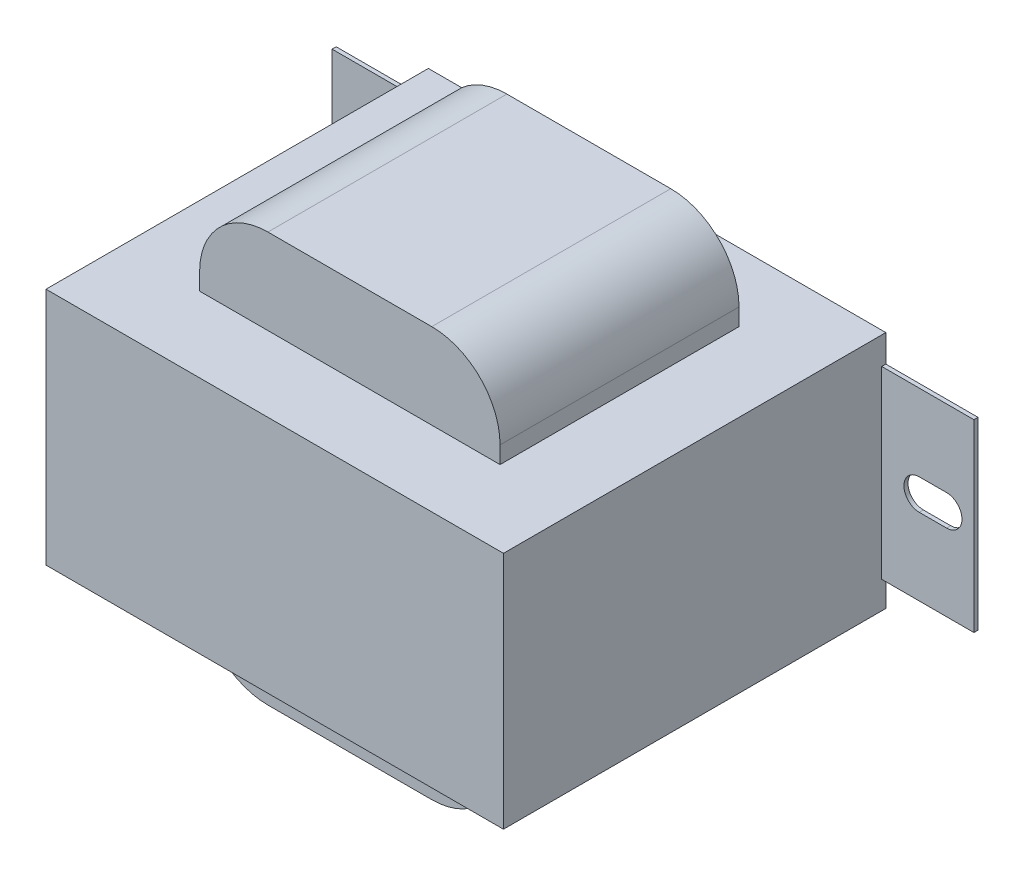
SolidWorks part; units mm, degrees
ref_plane "前视基准面" through (0, 0, 0) normal (0, 0, 1) x (1, 0, 0)
ref_plane "上视基准面" through (0, 0, 0) normal (0, 1, 0) x (1, 0, 0)
ref_plane "右视基准面" through (0, 0, 0) normal (1, 0, 0) x (0, 0, -1)
sketch "草图1" plane through (0, 0, 0) normal (0, 0, 1) x (1, 0, 0)
  line L0 (0, 78.0676) -> (0, -98.3955) construction
  line L1 (-33.5, 17.5) -> (33.5, 17.5)
  line L2 (-33.5, 17.5) -> (-33.5, -17.5)
  line L3 (-33.5, -17.5) -> (33.5, -17.5)
  line L4 (33.5, 17.5) -> (33.5, -17.5)
  line L5 (-98.6118, 0) -> (97.7467, 0) construction
  dimension "D1" = 35
  dimension "D2" = 67
extrude "拉伸1" add sketch "草图1" along normal blind 56
sketch "草图2" plane through (0, 0, 56) normal (0, 0, 1) x (1, 0, 0)
  line L1 (-12, 30) -> (12, 30)
  line L2 (-22, 20) -> (-22, -20)
  line L3 (-12, -30) -> (12, -30)
  line L4 (22, 20) -> (22, -20)
  arc A0 (-12, 30) -> (-22, 20) centre (-12, 20) ccw
  arc A1 (12, 30) -> (22, 20) centre (12, 20) cw
  arc A2 (-22, -20) -> (-12, -30) centre (-12, -20) ccw
  arc A3 (12, -30) -> (22, -20) centre (12, -20) ccw
  point P4 (0, 30)
  point P6 (-22, 0)
  point P9 (-22, 30)
  point P12 (22, 30)
  point P17 (22, -30)
  dimension "D3" = 10
  dimension "D1" = 44
  dimension "D2" = 60
extrude "拉伸2" add sketch "草图2" against normal blind 35 from offset 11 offset against normal yes
sketch "草图3" plane through (0, 0, 0) normal (0, 0, -1) x (-1, 0, 0)
  line L0 (-33.5, -17.5) -> (-33.5, 17.5) construction
  line L1 (-33.5, 13.5) -> (-47, 13.5)
  line L2 (-33.5, 13.5) -> (-33.5, -13.5)
  line L3 (-33.5, -13.5) -> (-47, -13.5)
  line L4 (-47, 13.5) -> (-47, -13.5)
  line L5 (-66.251, 0) -> (43.5792, 0) construction
  line L6 (-43, 0) -> (-39, 0) construction
  line L7 (-43, 2.25) -> (-39, 2.25)
  line L8 (-43, -2.25) -> (-39, -2.25)
  line L9 (43, 0) -> (39, 0) construction
  line L10 (0, 41.9816) -> (0, -49.4729) construction
  line L11 (43, 2.25) -> (39, 2.25)
  line L12 (43, -2.25) -> (39, -2.25)
  line L13 (47, 13.5) -> (47, -13.5)
  line L14 (33.5, -13.5) -> (47, -13.5)
  line L15 (33.5, 13.5) -> (33.5, -13.5)
  line L16 (33.5, 13.5) -> (47, 13.5)
  arc A0 (-43, 2.25) -> (-43, -2.25) centre (-43, 0) ccw
  arc A1 (-39, -2.25) -> (-39, 2.25) centre (-39, 0) ccw
  arc A2 (43, 2.25) -> (43, -2.25) centre (43, 0) cw
  arc A3 (39, -2.25) -> (39, 2.25) centre (39, 0) cw
  point P10 (-41, 0)
  point P19 (41, 0)
  dimension "D3" = 4
  dimension "D4" = 94
  dimension "D5" = 82
  dimension "D1" = 27
  dimension "D2" = 4.5
extrude "拉伸3" add sketch "草图3" against normal blind 0.6
